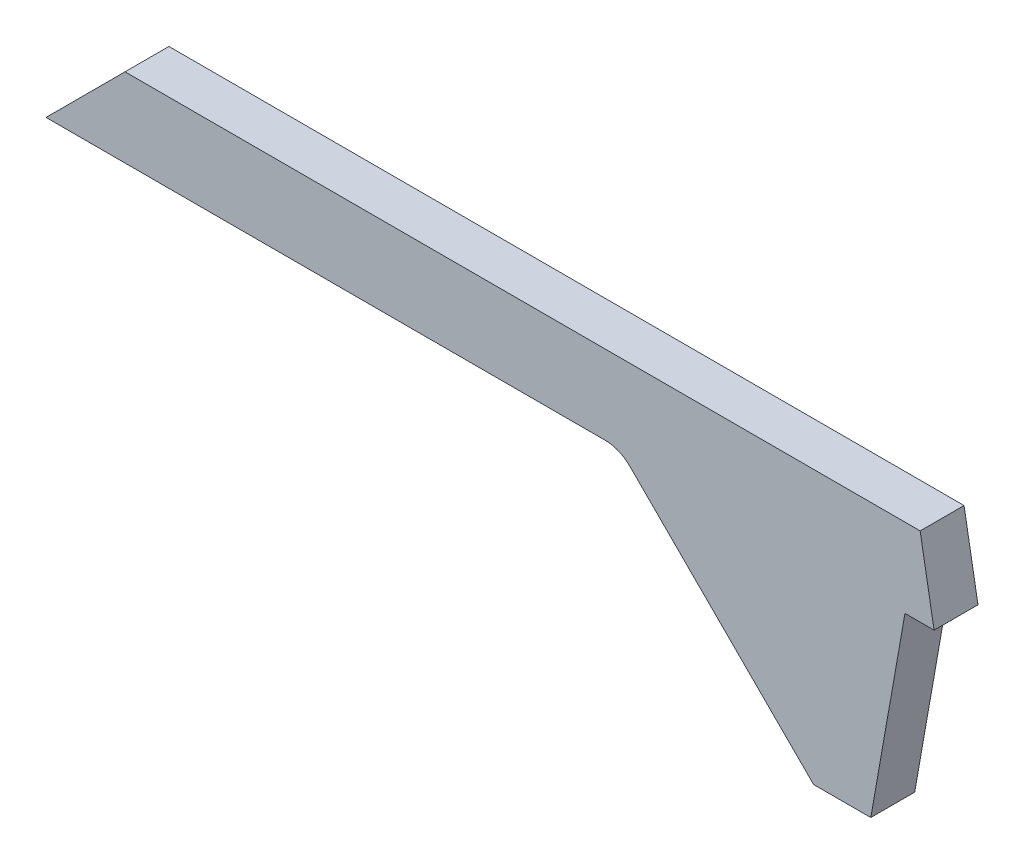
SolidWorks part; units mm, degrees
ref_plane "Front Plane" through (0, 0, 0) normal (0, 0, 1) x (1, 0, 0)
ref_plane "Top Plane" through (0, 0, 0) normal (0, 1, 0) x (1, 0, 0)
ref_plane "Right Plane" through (0, 0, 0) normal (1, 0, 0) x (0, 0, -1)
ref_axis "Axis1" through (0, -55, 0) along (0, 1, 0)
ref_plane "Plane1" through (0, 0, 93) normal (0, 0, 1) x (1, 0, 0)
sketch "Sketch1" plane through (0, 0, 93) normal (0, 0, 1) x (1, 0, 0)
  line L0 (786.6728, -234.2973) -> (778.4014, -234.2973)
  line L1 (786.6728, -234.2973) -> (778.4014, -234.2973)
  line L2 (751.84, -207.7359) -> (778.4014, -234.2973)
  line L3 (751.84, -207.7359) -> (778.4014, -234.2973)
  line L4 (748.2479, -206.248) -> (-621.2479, -206.248)
  line L5 (748.2479, -206.248) -> (667.3813, -206.248)
  line L6 (791.6187, -206.248) -> (786.6728, -234.2973)
  line L7 (791.6187, -206.248) -> (786.6728, -234.2973)
  line L8 (812.8, -206.248) -> (791.6187, -206.248)
  line L9 (-740.8187, -206.248) -> (-762, -206.248)
  line L11 (795.8302, -206.248) -> (791.6187, -206.248)
  line L12 (793.8148, -194.818) -> (795.8302, -206.248)
  line L13 (793.8148, -194.818) -> (795.8302, -206.248)
  line L14 (678.8113, -194.818) -> (793.8148, -194.818)
  line L15 (678.8113, -194.818) -> (793.8148, -194.818)
  line L16 (678.8113, -194.818) -> (668.5716, -205.0577)
  line L17 (678.8113, -194.818) -> (667.3813, -206.248)
  arc A0 (751.84, -207.7359) -> (748.2479, -206.248) centre (748.2479, -211.328) ccw
  arc A1 (751.84, -207.7359) -> (748.2479, -206.248) centre (748.2479, -211.328) ccw
extrude "Boss-Extrude1" add sketch "Sketch1" along normal mid plane 6.35
